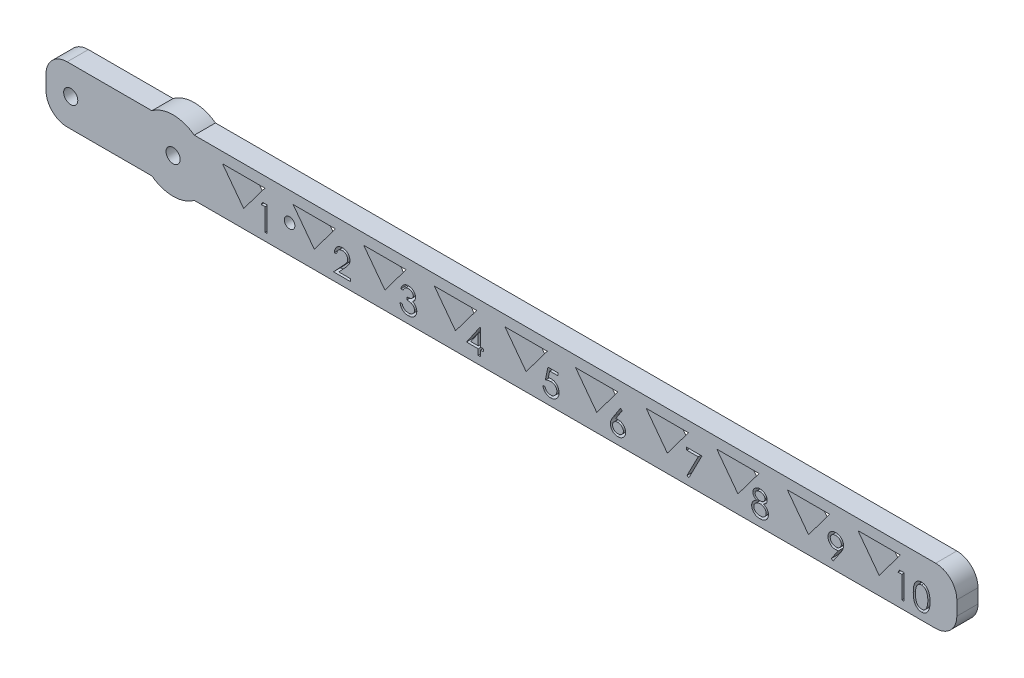
SolidWorks part; units mm, degrees
ref_plane "Plan de face" through (0, 0, 0) normal (0, 0, 1) x (1, 0, 0)
ref_plane "Plan de dessus" through (0, 0, 0) normal (0, 1, 0) x (1, 0, 0)
ref_plane "Plan de droite" through (0, 0, 0) normal (1, 0, 0) x (0, 0, -1)
sketch "Esquisse1" plane through (0, 0, 0) normal (0, 0, 1) x (1, 0, 0)
  line L1 (0, 0) -> (115, 0)
  line L2 (0, 0) -> (0, 8)
  line L3 (0, 8) -> (115, 8)
  line L4 (115, 0) -> (115, 8)
  dimension "D1" = 8
  dimension "D2" = 115
extrude "Boss.-Extru.1" add sketch "Esquisse1" against normal blind 3
sketch "Esquisse2" plane through (0, 0, 0) normal (0, 0, 1) x (1, 0, 0)
  line L0 (0, 8) -> (0, 0) construction
  line L1 (4, 4) -> (42.4373, 4) construction
  circle A0 centre (4, 4) radius 1
  circle A1 centre (20.5, 4) radius 0.75
  dimension "D1" = 2
  dimension "D2" = 4
  dimension "D3" = 1.5
  dimension "D4" = 16.5
extrude "Enlèv. mat.-Extru.1" cut sketch "Esquisse2" against normal through all
fillet "Congé1" radius 4 2 edges at (0, 0, -1.5) (0, 8, -1.5)
sketch "Esquisse3" plane through (0, 0, 0) normal (0, 0, 1) x (1, 0, 0)
  circle A0 centre (4, 4) radius 5
  circle A1 centre (4, 4) radius 2.75
  dimension "D1" = 10
extrude "Boss.-Extru.3" add sketch "Esquisse3" against normal blind 3
sketch "Esquisse4" plane through (0, 0, 0) normal (0, 0, 1) x (1, 0, 0)
  line L0 (11, 6.5) -> (17, 6.5)
  line L1 (17, 6.5) -> (14, 2.5)
  line L2 (14, 2.5) -> (11, 6.5)
  line L3 (115, 8) -> (7, 8) construction
  circle A0 centre (4, 4) radius 1 construction
  dimension "D1" = 6
  dimension "D2" = 5
  dimension "D3" = 5
  dimension "D4" = 1.5
  dimension "D5" = 10
extrude "Enlèv. mat.-Extru.2" cut sketch "Esquisse4" against normal through all
pattern_linear "Répétition linéaire1" count 10 spacing 10 along (1, 0, 0) of "Enlèv. mat.-Extru.2"
sketch "Esquisse5" plane through (0, 0, 0) normal (0, 0, 1) x (1, 0, 0)
  text T0 "1      2     3     4      5     6      7     8      9     10   11"
extrude "Enlèv. mat.-Extru.3" cut sketch "Esquisse5" against normal blind 1
sketch "Esquisse6" plane through (0, 0, -3) normal (0, 0, -1) x (-1, 0, 0)
  text T0 "11    10    9     8     7     6      5     4      3     2     1"
extrude "Enlèv. mat.-Extru.4" cut sketch "Esquisse6" against normal blind 1
sketch "Esquisse7" plane through (0, 0, 0) normal (0, 0, 1) x (1, 0, 0)
  line L0 (115, 8) -> (7, 8) construction
  line L1 (1, 8) -> (-11, 8)
  line L2 (1, 8) -> (1, 0)
  line L3 (1, 0) -> (-11, 0)
  line L4 (-14, 5) -> (-14, 3)
  line L5 (7, 0) -> (115, 0) construction
  line L6 (4, 4) -> (-17.4745, 4) construction
  arc A0 (7, 8) -> (7, 0) centre (4, 4) ccw construction
  circle A1 centre (-10.5, 4) radius 1
  arc A2 (-11, 0) -> (-14, 3) centre (-11, 3) cw
  arc A3 (-11, 8) -> (-14, 5) centre (-11, 5) ccw
  dimension "D2" = 2
  dimension "D4" = 3
  dimension "D1" = 14
  dimension "D3" = 14.5
extrude "Boss.-Extru.4" add sketch "Esquisse7" against normal up to surface (3 mm away) up to face at (89.5308, 2.7903, -3)
fillet "Congé2" radius 3 2 edges at (115, 0, -1.5) (115, 8, -1.5)
